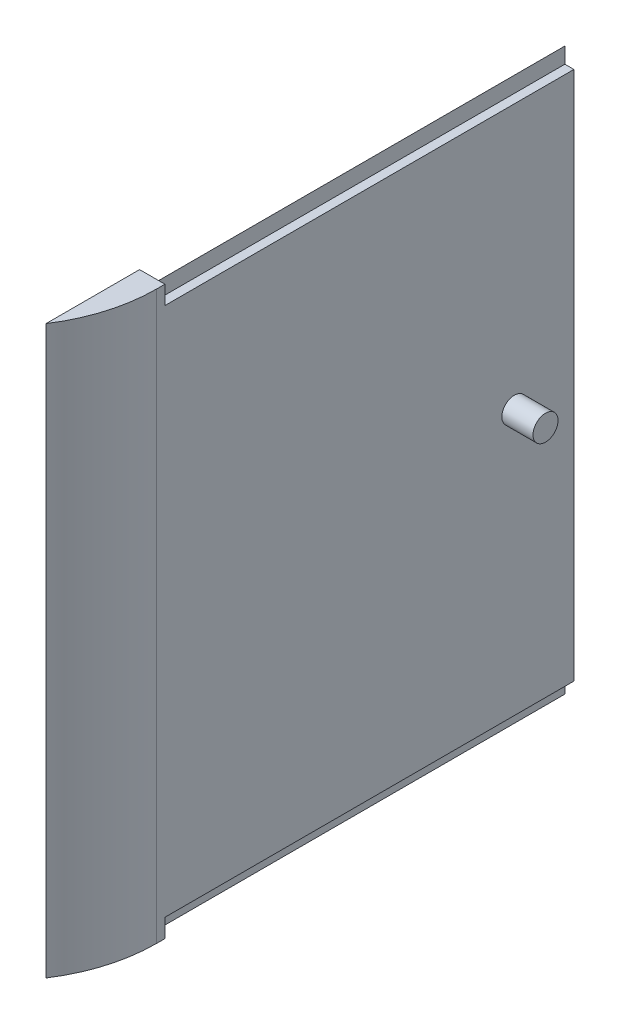
SolidWorks part; units mm, degrees
ref_plane "Front Plane" through (0, 0, 0) normal (0, 0, 1) x (1, 0, 0)
ref_plane "Top Plane" through (0, 0, 0) normal (0, 1, 0) x (1, 0, 0)
ref_plane "Right Plane" through (0, 0, 0) normal (1, 0, 0) x (0, 0, -1)
sketch "Sketch1" plane through (0, 0, 0) normal (0, 0, 1) x (1, 0, 0)
  line L0 (33.6841, -148) -> (37.6841, -148) construction
  line L1 (37.6841, -12) -> (37.6841, -7.95)
  line L2 (37.6841, -7.95) -> (33.6841, -12)
  line L3 (37.6841, -12) -> (33.6841, -12) construction
  line L8 (37.6841, -148) -> (40, -148)
  line L9 (37.6841, -152.05) -> (37.6841, -148)
  line L11 (33.6841, -148) -> (37.6841, -152.05)
  line L12 (37.6841, -12) -> (40, -12)
  line L16 (40, -12) -> (40, -148)
  line L18 (33.6841, -12) -> (33.6841, -148)
  dimension "D1" = 4.05
  dimension "D2" = 4
extrude "Boss-Extrude1" add sketch "Sketch1" against normal blind 105
sketch "Sketch4" plane through (0, 0, 0) normal (0, 0, 1) x (1, 0, 0)
  line L1 (40, -152.75) -> (33.5, -152.75)
  line L3 (40, -7.25) -> (33.5, -7.25)
  line L4 (33.5, -152.75) -> (33.5, -7.25)
  line L5 (40, -80) -> (33.5, -80) construction
  line L6 (40, -7.25) -> (40, -80)
  line L7 (40, -80) -> (40, -152.75)
  dimension "D1" = 145.5
  dimension "D2" = 6.5
extrude "Boss-Extrude2" add sketch "Sketch4" along normal blind 24
fillet "Fillet1" radius 40 1 edges at (40, -80, 24)
sketch "Sketch5" plane through (40, 0, 0) normal (1, 0, 0) x (0, 0, -1)
  line L0 (89.7148, -12) -> (89.7148, -148) construction
  line L1 (105, -12) -> (0, -12) construction
  line L2 (105, -148) -> (0, -148) construction
  circle A0 centre (89.7148, -80) radius 3.2191
extrude "Boss-Extrude3" add sketch "Sketch5" along normal blind 8
